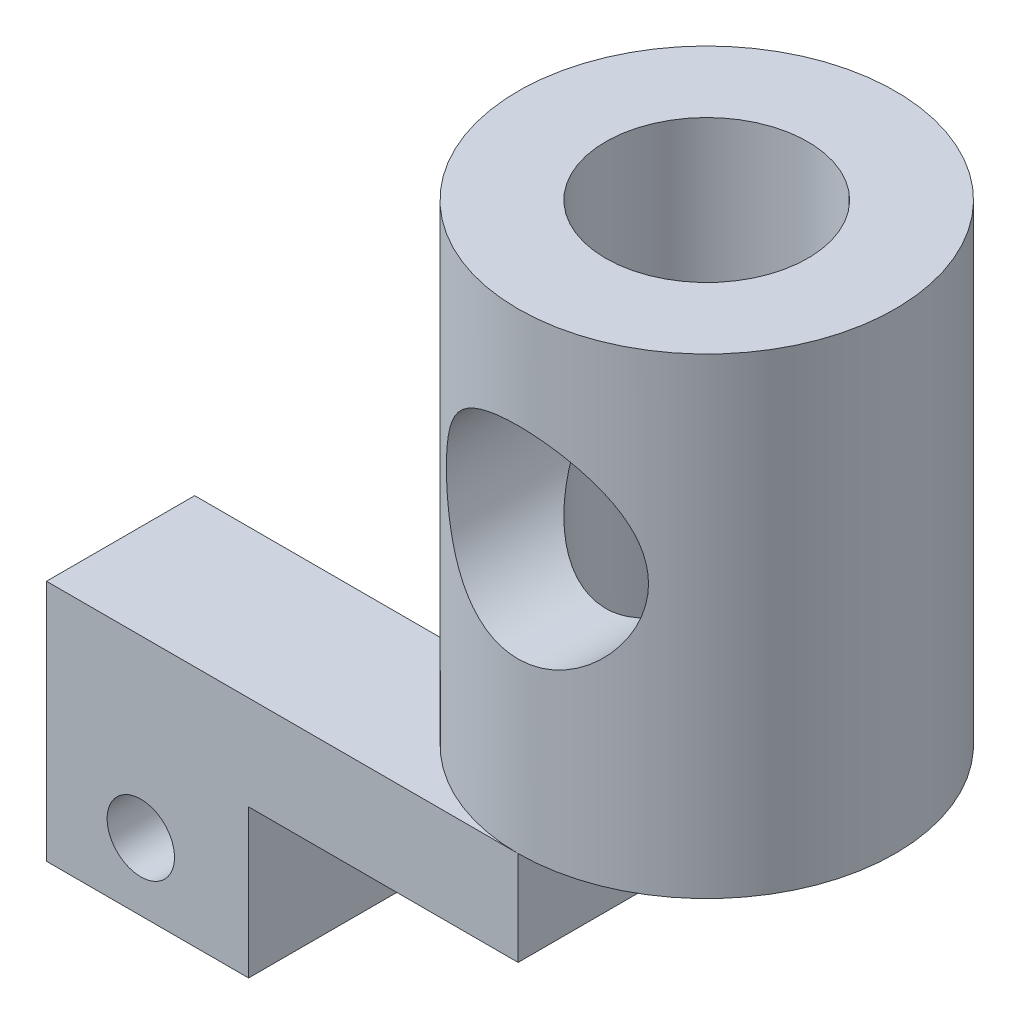
SolidWorks part; units mm, degrees
ref_plane "前视基准面" through (0, 0, 0) normal (0, 0, 1) x (1, 0, 0)
ref_plane "上视基准面" through (0, 0, 0) normal (0, 1, 0) x (1, 0, 0)
ref_plane "右视基准面" through (0, 0, 0) normal (1, 0, 0) x (0, 0, -1)
other "Configuration Table"
sketch "草图1" plane through (0, 0, 0) normal (0, 1, 0) x (1, 0, 0)
  line L0 (0, 0) -> (32.3829, 0) construction
  circle A0 centre (35, 0) radius 14
  circle A1 centre (35, 0) radius 7.5
  point P7 (0, 0)
  point P8 (0, 0)
  point P9 (0, 0)
  dimension "D1" = 28
  dimension "D2" = 15
  dimension "D3" = 35
extrude "凸台-拉伸1" add sketch "草图1" along normal blind 35
sketch "草图2" plane through (0, 0, 0) normal (0, 0, 1) x (1, 0, 0)
  circle A0 centre (35, 20) radius 7.5
  point P5 (2.6451, 13.1961)
  point P8 (-17.8632, 5.7982)
  dimension "D3" = 15
  dimension "D1" = 35
  dimension "D2" = 20
extrude "切除-拉伸1" cut sketch "草图2" along normal blind 35
sketch "草图3" plane through (0, 0, 0) normal (0, 0, 1) x (1, 0, 0)
  line L0 (0, 0) -> (35, 0)
  line L1 (21, 0) -> (49, 0) construction
  line L2 (35, 0) -> (35, -7)
  line L3 (35, -7) -> (15, -7)
  line L4 (15, -7) -> (15, -18)
  line L5 (15, -18) -> (0, -18)
  line L6 (0, -18) -> (0, 0)
  circle A0 centre (7, -13) radius 2.5
  point P13 (-12.2352, -5.5335)
  dimension "D5" = 5
  dimension "D1" = 11
  dimension "D2" = 15
  dimension "D3" = 7
  dimension "D4" = 5
  dimension "D6" = 7
extrude "凸台-拉伸2" add sketch "草图3" along normal blind 14
extrude "切除-拉伸2" cut sketch "草图3<2>" along normal blind 3
sketch "草图3<2>" plane through (0, 0, 0) normal (0, 0, 1) x (1, 0, 0) same geometry as "草图3"
